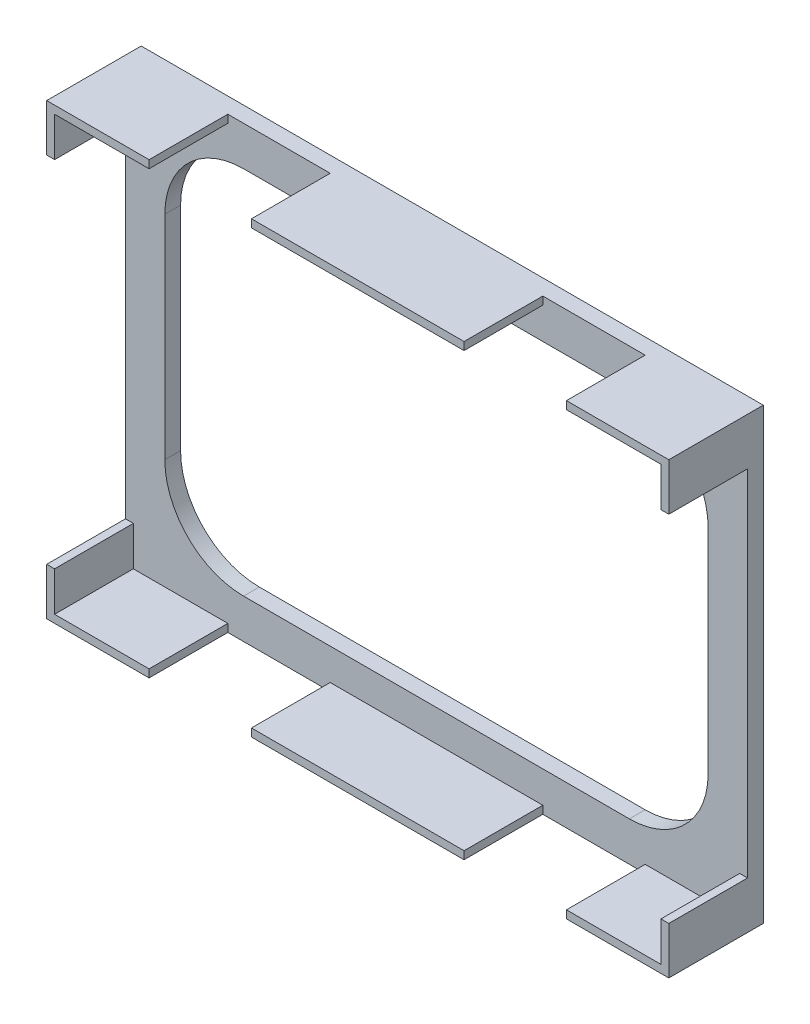
SolidWorks part; units mm, degrees
ref_plane "Front Plane" through (0, 0, 0) normal (0, 0, 1) x (1, 0, 0)
ref_plane "Top Plane" through (0, 0, 0) normal (0, 1, 0) x (1, 0, 0)
ref_plane "Right Plane" through (0, 0, 0) normal (1, 0, 0) x (0, 0, -1)
sketch "Sketch1" plane through (0, 0, 0) normal (0, 0, 1) x (1, 0, 0)
  line L1 (0, 0) -> (79, 0)
  line L2 (0, 0) -> (0, 57)
  line L3 (0, 57) -> (79, 57)
  line L4 (79, 0) -> (79, 57)
  dimension "D1" = 79
  dimension "D2" = 57
extrude "Boss-Extrude1" add sketch "Sketch1" along normal blind 12
sketch "Sketch2" plane through (0, 0, 12) normal (0, 0, 1) x (1, 0, 0)
  line L0 (5.1519, 0) -> (5.1519, 1) construction
  line L1 (0, 0) -> (79, 0) construction
  line L2 (73.574, 57) -> (73.574, 56) construction
  line L3 (79, 57) -> (0, 57) construction
  line L4 (0, 28.5) -> (79, 28.5) construction
  line L5 (0, 57) -> (0, 0) construction
  line L6 (79, 0) -> (79, 57) construction
  line L7 (5.1519, 57) -> (5.1519, 56) construction
  line L8 (73.574, 0) -> (73.574, 1) construction
  line L9 (0, 1) -> (1, 1) construction
  line L11 (1, 1) -> (78, 1)
  line L12 (1, 1) -> (1, 56)
  line L13 (1, 56) -> (78, 56)
  line L14 (78, 1) -> (78, 56)
  dimension "D1" = 77
extrude "Cut-Extrude1" cut sketch "Sketch2" against normal blind 10
sketch "Sketch3" plane through (79, 0, 0) normal (1, 0, 0) x (0, 0, -1)
  line L0 (-6, 0) -> (-6, 6) construction
  line L1 (-12, 0) -> (0, 0) construction
  line L2 (-6, 57) -> (-6, 51) construction
  line L3 (-12, 57) -> (0, 57) construction
  line L4 (0, 28.5) -> (-2, 28.5) construction
  line L5 (0, 0) -> (0, 57) construction
  line L11 (-12, 0) -> (-12, 57) construction
  line L12 (-2, 6) -> (-12, 6)
  line L13 (-2, 6) -> (-2, 51)
  line L14 (-2, 51) -> (-12, 51)
  line L15 (-12, 6) -> (-12, 51)
  dimension "D1" = 6
  dimension "D2" = 6
extrude "Cut-Extrude3" cut sketch "Sketch3" against normal blind 100
sketch "Sketch4" plane through (0, 0, 0) normal (0, -1, 0) x (-1, 0, 0)
  line L0 (0, -6) -> (-6, -6) construction
  line L1 (-79, -6) -> (-73, -6) construction
  line L2 (0, -12) -> (0, 0) construction
  line L3 (-79, -12) -> (-79, 0) construction
  line L4 (-39.5, 0) -> (-39.5, -2) construction
  line L5 (0, 0) -> (-79, 0) construction
  line L6 (0, -12) -> (-79, -12) construction
  line L9 (-5, -12) -> (-74, -12)
  line L12 (-6, -2) -> (-73, -2)
  line L13 (-6, -2) -> (-6, -12)
  line L14 (-6, -12) -> (-73, -12)
  line L15 (-73, -2) -> (-73, -12)
extrude "Cut-Extrude4" cut sketch "Sketch4" against normal blind 100 rebuild error yes
sketch "Sketch6" plane through (0, 0, 0) normal (0, -1, 0) x (1, 0, 0)
  line L0 (0, 6) -> (13, 6) construction
  line L1 (0, 12) -> (0, 0) construction
  line L2 (79, 6) -> (66, 6) construction
  line L3 (79, 12) -> (79, 0) construction
  line L4 (39.5, 0) -> (39.5, 2) construction
  line L5 (0, 0) -> (79, 0) construction
  line L6 (13, 12) -> (26, 12) construction
  line L11 (13, 0) -> (13, 12) construction
  line L12 (0, 12) -> (79, 12) construction
  line L13 (26, 12) -> (26, 0) construction
  line L14 (66, 0) -> (66, 12) construction
  line L15 (66, 12) -> (53, 12) construction
  line L16 (53, 12) -> (53, 0) construction
  line L18 (13, 2) -> (26, 2)
  line L19 (13, 2) -> (13, 12)
  line L20 (13, 12) -> (26, 12)
  line L21 (26, 2) -> (26, 12)
  line L22 (53, 2) -> (66, 2)
  line L23 (53, 2) -> (53, 12)
  line L24 (53, 12) -> (66, 12)
  line L25 (66, 2) -> (66, 12)
extrude "Cut-Extrude5" cut sketch "Sketch6" against normal blind 100
sketch "Sketch7" plane through (0, 0, 2) normal (0, 0, 1) x (1, 0, 0)
  line L0 (79, 28.5) -> (74, 28.5) construction
  line L1 (79, 6) -> (79, 51) construction
  line L2 (70.117, 0) -> (70.117, 5) construction
  line L3 (13, 0) -> (66, 0) construction
  line L4 (0, 43.6548) -> (5, 43.6548) construction
  line L5 (0, 6) -> (0, 51) construction
  line L6 (18.9006, 57) -> (18.9006, 52) construction
  line L7 (13, 57) -> (66, 57) construction
  line L9 (5, 52) -> (74, 52)
  line L10 (5, 52) -> (5, 5)
  line L11 (5, 5) -> (74, 5)
  line L12 (74, 52) -> (74, 5)
extrude "Cut-Extrude7" cut sketch "Sketch7" against normal blind 10
fillet "Fillet1" radius 10 1 edges at (5, 52, 1)
fillet "Fillet2" radius 10 1 edges at (5, 5, 1)
fillet "Fillet3" radius 10 1 edges at (74, 5, 1)
fillet "Fillet4" radius 10 1 edges at (74, 52, 1)
